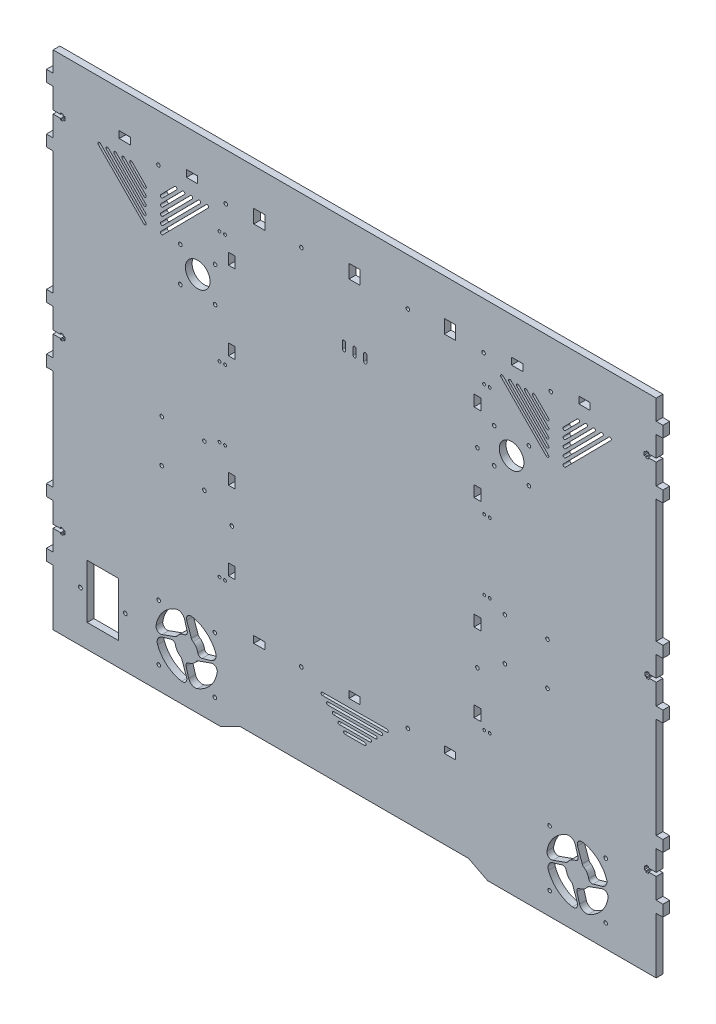
SolidWorks part; units mm, degrees
material "Клен"
ref_plane "Front" through (0, 0, 0) normal (0, 0, 1) x (1, 0, 0)
ref_plane "Top" through (0, 0, 0) normal (0, 1, 0) x (1, 0, 0)
ref_plane "Right" through (0, 0, 0) normal (1, 0, 0) x (0, 0, -1)
sketch "Эскиз1" plane through (0, 0, 0) normal (0, 0, 1) x (1, 0, 0)
  line L3 (1048.7554, 42.0072) -> (1198.2753, 42.0072)
  line L6 (1048.7554, 490.0072) -> (1586.0184, 490.0072)
  line L12 (1586.7554, 42.6812) -> (1586.7554, 42.0072)
  line L13 (1397.7554, 445.0072) -> (1407.7554, 445.0072)
  line L14 (1407.7554, 445.0072) -> (1407.7554, 457.1072)
  line L15 (1407.7554, 457.1072) -> (1397.7554, 457.1072)
  line L16 (1397.7554, 457.1072) -> (1397.7554, 445.0072)
  line L17 (1048.7554, 42.6769) -> (1048.7554, 42.0072)
  line L19 (1503.9666, 426.2291) -> (1516.2724, 438.6716)
  line L20 (1546.3337, 437.0699) -> (1505.9003, 396.1873)
  line L21 (1227.7554, 445.0072) -> (1237.7554, 445.0072)
  line L22 (1237.7554, 445.0072) -> (1237.7554, 457.1072)
  line L23 (1237.7554, 457.1072) -> (1227.7554, 457.1072)
  line L24 (1227.7554, 457.1072) -> (1227.7554, 445.0072)
  line L25 (1312.7554, 445.0072) -> (1322.7554, 445.0072)
  line L26 (1322.7554, 445.0072) -> (1322.7554, 457.1072)
  line L27 (1322.7554, 457.1072) -> (1312.7554, 457.1072)
  line L28 (1312.7554, 457.1072) -> (1312.7554, 445.0072)
  line L38 (1525.1209, 436.9527) -> (1505.7831, 417.4001)
  line L41 (1504.0838, 405.0162) -> (1537.4853, 438.7888)
  line L43 (1504.1228, 397.9452) -> (1544.5562, 438.8279)
  line L44 (1504.0056, 419.1581) -> (1523.3433, 438.7107)
  line L48 (1167.7554, 451.0072) -> (1177.7554, 451.0072)
  line L49 (1177.7554, 451.0072) -> (1177.7554, 457.1072)
  line L50 (1177.7554, 457.1072) -> (1167.7554, 457.1072)
  line L51 (1167.7554, 457.1072) -> (1167.7554, 451.0072)
  line L52 (1518.0499, 436.9136) -> (1505.7441, 424.4711)
  line L53 (1532.1918, 436.9918) -> (1505.8222, 410.3292)
  line L54 (1539.2628, 437.0308) -> (1505.8613, 403.2582)
  line L55 (1504.0447, 412.0872) -> (1530.4143, 438.7498)
  line L56 (1457.7554, 451.0072) -> (1467.7554, 451.0072)
  line L57 (1467.7554, 451.0072) -> (1467.7554, 457.1072)
  line L58 (1467.7554, 457.1072) -> (1457.7554, 457.1072)
  line L59 (1457.7554, 457.1072) -> (1457.7554, 451.0072)
  line L78 (1131.3881, 397.9452) -> (1090.9547, 438.8279)
  line L80 (1089.1772, 437.0699) -> (1129.6105, 396.1873)
  line L82 (1096.2481, 437.0308) -> (1129.6496, 403.2582)
  line L83 (1131.4271, 405.0162) -> (1098.0256, 438.7888)
  line L84 (1131.4662, 412.0872) -> (1105.0966, 438.7498)
  line L85 (1103.3191, 436.9918) -> (1129.6887, 410.3292)
  line L86 (1131.5052, 419.1581) -> (1112.1675, 438.7107)
  line L87 (1110.39, 436.9527) -> (1129.7277, 417.4001)
  line L88 (1131.5443, 426.2291) -> (1119.2385, 438.6716)
  line L89 (1117.461, 436.9136) -> (1129.7668, 424.4711)
  line L90 (1144.921, 397.9452) -> (1185.3543, 438.8279)
  line L91 (1187.1318, 437.0699) -> (1146.6985, 396.1873)
  line L92 (1397.7554, 121.0049) -> (1407.7554, 121.0049)
  line L93 (1407.7554, 121.0049) -> (1407.7554, 127.1049)
  line L94 (1407.7554, 127.1049) -> (1397.7554, 127.1049)
  line L95 (1397.7554, 127.1049) -> (1397.7554, 121.0049)
  line L96 (1312.7554, 121.0049) -> (1322.7554, 121.0049)
  line L97 (1322.7554, 121.0049) -> (1322.7554, 127.1049)
  line L98 (1322.7554, 127.1049) -> (1312.7554, 127.1049)
  line L99 (1312.7554, 127.1049) -> (1312.7554, 121.0049)
  line L100 (1227.7554, 121.0049) -> (1237.7554, 121.0049)
  line L101 (1237.7554, 121.0049) -> (1237.7554, 127.1049)
  line L102 (1237.7554, 127.1049) -> (1227.7554, 127.1049)
  line L143 (1227.7554, 127.1049) -> (1227.7554, 121.0049)
  line L148 (1079.1628, 110.8776) -> (1079.1628, 62.8776)
  line L154 (1455.45, 437.0308) -> (1488.8515, 403.2582)
  line L159 (1107.1628, 110.8776) -> (1079.1628, 110.8776)
  line L160 (1079.1628, 62.8776) -> (1107.1628, 62.8776)
  line L161 (1107.1628, 62.8776) -> (1107.1628, 110.8776)
  line L162 (1144.8819, 405.0162) -> (1178.2834, 438.7888)
  line L163 (1180.0609, 437.0308) -> (1146.6594, 403.2582)
  line L164 (1172.9899, 436.9918) -> (1146.6203, 410.3292)
  line L165 (1144.8428, 412.0872) -> (1171.2124, 438.7498)
  line L166 (1144.8038, 419.1581) -> (1164.1415, 438.7107)
  line L167 (1165.919, 436.9527) -> (1146.5813, 417.4001)
  line L168 (1158.848, 436.9136) -> (1146.5422, 424.4711)
  line L169 (1144.7647, 426.2291) -> (1157.0705, 438.6716)
  line L172 (1326.6292, 91.6177) -> (1309.1294, 91.521)
  line L173 (1309.1156, 94.021) -> (1326.6154, 94.1176)
  line L174 (1331.6015, 96.6452) -> (1304.1019, 96.4933)
  line L175 (1304.0881, 98.9933) -> (1331.5877, 99.1452)
  line L176 (1336.5738, 101.6728) -> (1299.0744, 101.4656)
  line L177 (1299.0605, 103.9656) -> (1336.56, 104.1727)
  line L178 (1289.0054, 113.9102) -> (1346.5046, 114.2278)
  line L179 (1346.5184, 111.7279) -> (1289.0193, 111.4102)
  line L180 (1341.5461, 106.7003) -> (1294.0468, 106.4379)
  line L181 (1294.033, 108.9379) -> (1341.5323, 109.2003)
  line L182 (1490.629, 405.0162) -> (1457.2275, 438.7888)
  line L183 (1448.379, 437.0699) -> (1488.8124, 396.1873)
  line L184 (1469.5919, 436.9527) -> (1488.9296, 417.4001)
  line L185 (1476.6629, 436.9136) -> (1488.9687, 424.4711)
  line L186 (1490.5899, 397.9452) -> (1450.1565, 438.8279)
  line L187 (1490.7071, 419.1581) -> (1471.3694, 438.7107)
  line L188 (1462.521, 436.9918) -> (1488.8906, 410.3292)
  line L189 (1490.7462, 426.2291) -> (1478.4404, 438.6716)
  line L198 (1530.3174, 86.3769) -> (1538.4752, 88.7337)
  line L199 (1494.5571, 86.9094) -> (1506.2002, 91.0661)
  line L200 (1517.0418, 100.6255) -> (1514.685, 108.7833)
  line L201 (1502.7664, 87.3542) -> (1494.6086, 84.9974)
  line L202 (1538.538, 86.8062) -> (1526.8948, 82.6495)
  line L203 (1516.0532, 73.09) -> (1518.4101, 64.9322)
  line L204 (1516.4826, 64.8695) -> (1512.3258, 76.5127)
  line L205 (1516.6012, 108.8616) -> (1520.758, 97.2184)
  line L210 (1215.2753, 50.7072) -> (1198.2753, 42.0072)
  line L268 (1215.2753, 50.7072) -> (1419.2753, 50.7072)
  line L269 (1419.2753, 50.7072) -> (1436.2753, 42.0072)
  line L270 (1436.2753, 42.0072) -> (1586.7554, 42.0072)
  line L271 (1490.6681, 412.0872) -> (1464.2985, 438.7498)
  line L302 (1527.7554, 457.1072) -> (1517.7554, 457.1072)
  line L303 (1517.7554, 451.0072) -> (1527.7554, 451.0072)
  line L304 (1517.7554, 457.1072) -> (1517.7554, 451.0072)
  line L305 (1527.7554, 451.0072) -> (1527.7554, 457.1072)
  line L306 (1117.7554, 451.0072) -> (1117.7554, 457.1072)
  line L307 (1107.7554, 457.1072) -> (1107.7554, 451.0072)
  line L308 (1117.7554, 457.1072) -> (1107.7554, 457.1072)
  line L309 (1107.7554, 451.0072) -> (1117.7554, 451.0072)
  line L310 (1167.825, 64.8695) -> (1163.6683, 76.5127)
  line L348 (1592.7554, 462.0158) -> (1586.7554, 461.9158)
  line L358 (1059.2554, 440.4572) -> (1059.2554, 443.5572)
  line L359 (1057.7554, 439.2572) -> (1057.7554, 440.4572)
  line L360 (1048.7554, 477.0072) -> (1048.7554, 490.0072)
  line L361 (1057.7554, 270.4572) -> (1059.2554, 270.4572)
  line L362 (1055.5554, 270.4572) -> (1055.5554, 269.2572)
  line L363 (1430.3554, 401.9072) -> (1430.3554, 411.9072)
  line L364 (1430.3554, 411.9072) -> (1424.2554, 411.9072)
  line L365 (1424.2554, 411.9072) -> (1424.2554, 401.9072)
  line L366 (1424.2554, 401.9072) -> (1430.3554, 401.9072)
  line L367 (1430.3554, 331.9072) -> (1430.3554, 341.9072)
  line L368 (1430.3554, 341.9072) -> (1424.2554, 341.9072)
  line L369 (1424.2554, 341.9072) -> (1424.2554, 331.9072)
  line L370 (1424.2554, 331.9072) -> (1430.3554, 331.9072)
  line L371 (1430.3554, 231.9072) -> (1430.3554, 241.9072)
  line L372 (1430.3554, 241.9072) -> (1424.2554, 241.9072)
  line L373 (1424.2554, 241.9072) -> (1424.2554, 231.9072)
  line L374 (1424.2554, 231.9072) -> (1430.3554, 231.9072)
  line L375 (1424.2554, 171.9072) -> (1424.2554, 161.9072)
  line L376 (1424.2554, 161.9072) -> (1430.3554, 161.9072)
  line L377 (1430.3554, 161.9072) -> (1430.3554, 171.9072)
  line L378 (1430.3554, 171.9072) -> (1424.2554, 171.9072)
  line L379 (1205.1554, 161.9072) -> (1211.2554, 161.9072)
  line L380 (1211.2554, 161.9072) -> (1211.2554, 171.9072)
  line L381 (1205.1554, 171.9072) -> (1205.1554, 161.9072)
  line L382 (1211.2554, 171.9072) -> (1205.1554, 171.9072)
  line L383 (1211.2554, 231.9072) -> (1211.2554, 241.9072)
  line L384 (1211.2554, 241.9072) -> (1205.1554, 241.9072)
  line L385 (1205.1554, 241.9072) -> (1205.1554, 231.9072)
  line L386 (1205.1554, 231.9072) -> (1211.2554, 231.9072)
  line L387 (1205.1554, 331.9072) -> (1211.2554, 331.9072)
  line L388 (1211.2554, 331.9072) -> (1211.2554, 341.9072)
  line L389 (1205.1554, 341.9072) -> (1205.1554, 331.9072)
  line L390 (1211.2554, 341.9072) -> (1205.1554, 341.9072)
  line L391 (1205.1554, 401.9072) -> (1211.2554, 401.9072)
  line L392 (1211.2554, 401.9072) -> (1211.2554, 411.9072)
  line L393 (1211.2554, 411.9072) -> (1205.1554, 411.9072)
  line L394 (1205.1554, 411.9072) -> (1205.1554, 401.9072)
  line L395 (1145.8995, 86.9094) -> (1157.5427, 91.0661)
  line L396 (1189.8804, 86.8062) -> (1178.2373, 82.6495)
  line L397 (1167.3957, 73.09) -> (1169.7525, 64.9322)
  line L398 (1154.1089, 87.3542) -> (1145.951, 84.9974)
  line L399 (1181.6599, 86.3769) -> (1189.8177, 88.7337)
  line L400 (1167.9437, 108.8616) -> (1172.1004, 97.2184)
  line L414 (1057.7554, 119.2572) -> (1057.7554, 120.4572)
  line L415 (1168.3843, 100.6255) -> (1166.0274, 108.7833)
  line L416 (1317.7554, 12.4246) -> (1317.7554, 537.1765) construction
  line L417 (1586.7554, 537.1765) -> (1586.7554, 12.4246) construction
  line L418 (1048.7554, 537.1765) -> (1048.7554, -11.6164) construction
  line L419 (1042.7554, 92.0072) -> (1042.7554, 102.0072)
  line L422 (1048.7554, 123.5572) -> (1048.7554, 141.9072)
  line L423 (1048.7554, 472.1072) -> (1048.7554, 477.0072)
  line L426 (1059.2554, 123.5572) -> (1057.7554, 123.5572)
  line L427 (1057.7554, 274.7572) -> (1055.5554, 274.7572)
  line L428 (1325.8554, 394.0442) -> (1325.8554, 388.0442)
  line L429 (1328.6554, 388.0442) -> (1328.6554, 394.0442)
  line L430 (1042.7554, 102.0072) -> (1048.7554, 102.1072)
  line L431 (1057.7554, 120.4572) -> (1059.2554, 120.4572)
  line L432 (1316.3554, 394.0442) -> (1316.3554, 388.0442)
  line L433 (1319.1554, 388.0442) -> (1319.1554, 394.0442)
  line L434 (1042.7554, 142.0072) -> (1042.7554, 152.0072)
  line L435 (1042.7554, 302.0072) -> (1048.7554, 302.1072)
  line L436 (1306.8554, 394.0442) -> (1306.8554, 388.0442)
  line L437 (1309.6554, 388.0442) -> (1309.6554, 394.0442)
  line L438 (1055.5554, 120.4572) -> (1055.5554, 119.2572)
  line L439 (1048.7554, 411.9072) -> (1042.7554, 412.0072)
  line L440 (1055.5554, 444.7572) -> (1055.5554, 443.5572)
  line L441 (1057.7554, 124.7572) -> (1055.5554, 124.7572)
  line L442 (1055.5554, 443.5572) -> (1048.7554, 443.5572)
  line L443 (1048.7554, 120.4572) -> (1055.5554, 120.4572)
  line L444 (1042.7554, 242.0072) -> (1042.7554, 252.0072)
  line L445 (1055.5554, 269.2572) -> (1057.7554, 269.2572)
  line L446 (1055.5554, 274.7572) -> (1055.5554, 273.5572)
  line L447 (1048.7554, 461.9072) -> (1042.7554, 462.0072)
  line L448 (1048.7554, 102.1072) -> (1048.7554, 120.4572)
  line L449 (1057.7554, 440.4572) -> (1059.2554, 440.4572)
  line L450 (1048.7554, 252.1072) -> (1048.7554, 270.4572)
  line L451 (1042.7554, 292.0072) -> (1042.7554, 302.0072)
  line L452 (1042.7554, 472.0072) -> (1048.7554, 472.1072)
  line L453 (1059.2554, 443.5572) -> (1057.7554, 443.5572)
  line L454 (1048.7554, 42.6769) -> (1048.7554, 91.9072)
  line L455 (1048.7554, 273.5572) -> (1048.7554, 291.9072)
  line L456 (1055.5554, 440.4572) -> (1055.5554, 439.2572)
  line L457 (1055.5554, 439.2572) -> (1057.7554, 439.2572)
  line L458 (1042.7554, 422.0072) -> (1048.7554, 422.1072)
  line L459 (1048.7554, 443.5572) -> (1048.7554, 461.9072)
  line L460 (1048.7554, 141.9072) -> (1042.7554, 142.0072)
  line L461 (1048.7554, 302.1072) -> (1048.7554, 411.9072)
  line L462 (1048.7554, 91.9072) -> (1042.7554, 92.0072)
  line L463 (1048.7554, 270.4572) -> (1055.5554, 270.4572)
  line L464 (1048.7554, 291.9072) -> (1042.7554, 292.0072)
  line L465 (1059.2554, 120.4572) -> (1059.2554, 123.5572)
  line L466 (1057.7554, 273.5572) -> (1057.7554, 274.7572)
  line L467 (1042.7554, 252.0072) -> (1048.7554, 252.1072)
  line L468 (1059.2554, 273.5572) -> (1057.7554, 273.5572)
  line L469 (1048.7554, 422.1072) -> (1048.7554, 440.4572)
  line L470 (1042.7554, 462.0072) -> (1042.7554, 472.0072)
  line L471 (1057.7554, 269.2572) -> (1057.7554, 270.4572)
  line L472 (1057.7554, 443.5572) -> (1057.7554, 444.7572)
  line L473 (1042.7554, 152.0072) -> (1048.7554, 152.1072)
  line L474 (1059.2554, 270.4572) -> (1059.2554, 273.5572)
  line L475 (1055.5554, 273.5572) -> (1048.7554, 273.5572)
  line L476 (1048.7554, 152.1072) -> (1048.7554, 241.9072)
  line L477 (1057.7554, 444.7572) -> (1055.5554, 444.7572)
  line L478 (1055.5554, 124.7572) -> (1055.5554, 123.5572)
  line L479 (1048.7554, 241.9072) -> (1042.7554, 242.0072)
  line L480 (1055.5554, 123.5572) -> (1048.7554, 123.5572)
  line L481 (1057.7554, 123.5572) -> (1057.7554, 124.7572)
  line L482 (1055.5554, 119.2572) -> (1057.7554, 119.2572)
  line L483 (1042.7554, 412.0072) -> (1042.7554, 422.0072)
  line L484 (1048.7554, 440.4572) -> (1055.5554, 440.4572)
  line L487 (1586.0184, 490.0072) -> (1586.7554, 490.0072)
  line L488 (1586.7554, 302.1072) -> (1592.7554, 302.0072)
  line L489 (1592.7554, 252.0072) -> (1592.7554, 242.0072)
  line L490 (1579.6985, 444.7615) -> (1577.4985, 444.7615)
  line L491 (1592.7554, 472.0072) -> (1592.7554, 462.0158)
  line L492 (1579.9554, 120.4572) -> (1586.7554, 120.4572)
  line L493 (1592.7554, 102.0072) -> (1592.7554, 92.0072)
  line L494 (1579.9554, 123.5572) -> (1579.9554, 124.7572)
  line L495 (1586.7554, 490.0072) -> (1586.7554, 472.1072)
  line L496 (1577.7554, 120.4572) -> (1577.7554, 119.2572)
  line L497 (1578.2356, 269.2572) -> (1580.4356, 269.2572)
  line L498 (1575.9985, 440.4615) -> (1577.4985, 440.4615)
  line L499 (1580.4356, 274.7572) -> (1578.2356, 274.7572)
  line L500 (1577.7554, 123.5572) -> (1576.2554, 123.5572)
  line L501 (1576.7356, 273.5572) -> (1576.7356, 270.4572)
  line L502 (1586.4985, 443.5615) -> (1586.7554, 443.5615)
  line L503 (1578.2356, 274.7572) -> (1578.2356, 273.5572)
  line L504 (1577.4985, 439.2615) -> (1579.6985, 439.2615)
  line L505 (1576.2554, 120.4572) -> (1577.7554, 120.4572)
  line L506 (1586.4985, 443.5615) -> (1579.6985, 443.5615)
  line L507 (1586.7554, 141.9072) -> (1586.7554, 123.5572)
  line L508 (1592.7554, 142.0072) -> (1586.7554, 141.9072)
  line L509 (1586.7554, 252.1072) -> (1592.7554, 252.0072)
  line L510 (1578.2356, 270.4572) -> (1578.2356, 269.2572)
  line L511 (1580.4356, 270.4572) -> (1586.7554, 270.4572)
  line L512 (1579.9554, 124.7572) -> (1577.7554, 124.7572)
  line L513 (1577.7554, 124.7572) -> (1577.7554, 123.5572)
  line L514 (1592.7554, 142.0072) -> (1592.7554, 152.0072)
  line L515 (1579.6985, 440.4615) -> (1586.4985, 440.4615)
  line L516 (1592.7554, 412.0072) -> (1586.7554, 411.9072)
  line L517 (1580.4356, 269.2572) -> (1580.4356, 270.4572)
  line L518 (1586.7554, 91.9072) -> (1586.7554, 42.6812)
  line L519 (1592.7554, 242.0072) -> (1586.7554, 241.9072)
  line L520 (1579.6985, 439.2615) -> (1579.6985, 440.4615)
  line L521 (1580.4356, 273.5572) -> (1580.4356, 274.7572)
  line L522 (1586.7554, 270.4572) -> (1586.7554, 252.1072)
  line L523 (1577.4985, 443.5615) -> (1575.9985, 443.5615)
  line L524 (1586.7554, 152.1072) -> (1592.7554, 152.0072)
  line L525 (1577.7554, 119.2572) -> (1579.9554, 119.2572)
  line L526 (1592.7554, 422.0072) -> (1592.7554, 412.0072)
  line L527 (1586.7554, 422.1072) -> (1592.7554, 422.0072)
  line L528 (1579.9554, 119.2572) -> (1579.9554, 120.4572)
  line L529 (1586.7554, 273.5572) -> (1580.4356, 273.5572)
  line L530 (1586.7554, 123.5572) -> (1579.9554, 123.5572)
  line L531 (1586.4985, 440.4615) -> (1586.7554, 440.4615)
  line L532 (1576.7356, 270.4572) -> (1578.2356, 270.4572)
  line L533 (1586.7554, 461.9158) -> (1586.7554, 443.5615)
  line L534 (1575.9985, 443.5615) -> (1575.9985, 440.4615)
  line L535 (1592.7554, 292.0072) -> (1586.7554, 291.9072)
  line L536 (1586.7554, 120.4572) -> (1586.7554, 102.1072)
  line L537 (1576.2554, 123.5572) -> (1576.2554, 120.4572)
  line L538 (1586.7554, 102.1072) -> (1592.7554, 102.0072)
  line L539 (1592.7554, 92.0072) -> (1586.7554, 91.9072)
  line L540 (1586.7554, 411.9072) -> (1586.7554, 302.1072)
  line L541 (1592.7554, 302.0072) -> (1592.7554, 292.0072)
  line L542 (1577.4985, 444.7615) -> (1577.4985, 443.5615)
  line L543 (1579.6985, 443.5615) -> (1579.6985, 444.7615)
  line L544 (1586.7554, 241.9072) -> (1586.7554, 152.1072)
  line L545 (1586.7554, 440.4615) -> (1586.7554, 422.1072)
  line L546 (1586.7554, 291.9072) -> (1586.7554, 273.5572)
  line L547 (1578.2356, 273.5572) -> (1576.7356, 273.5572)
  line L548 (1586.7554, 472.1072) -> (1592.7554, 472.0072)
  line L549 (1577.4985, 440.4615) -> (1577.4985, 439.2615)
  circle A0 centre (1193.2554, 365.5072) radius 1.6
  circle A1 centre (1162.2554, 365.5072) radius 1.6
  circle A2 centre (1177.7554, 381.0072) radius 11
  circle A3 centre (1193.2554, 396.5072) radius 1.6
  circle A4 centre (1202.7554, 448.0572) radius 1.6
  circle A5 centre (1432.7554, 448.0572) radius 1.6
  circle A6 centre (1365.2554, 448.0572) radius 1.6
  circle A7 centre (1270.2554, 448.0572) radius 1.6
  circle A12 centre (1162.2554, 396.5072) radius 1.6
  circle A13 centre (1145.7129, 217.2739) radius 1.6
  circle A14 centre (1365.2554, 124.0549) radius 1.6
  circle A15 centre (1270.2554, 124.0549) radius 1.6
  circle A20 centre (1492.7554, 448.0572) radius 1.6
  circle A21 centre (1142.7554, 448.0572) radius 1.6
  circle A24 centre (1073.1628, 86.8776) radius 1.65
  circle A25 centre (1113.1628, 86.8776) radius 1.65
  circle A26 centre (1145.7129, 255.2739) radius 1.6
  circle A27 centre (1183.7129, 217.2739) radius 1.6
  circle A28 centre (1183.7129, 255.2739) radius 1.6
  arc A29 (1504.0056, 419.1581) -> (1505.7831, 417.4001) centre (1504.8944, 418.2791) ccw
  arc A30 (1503.9666, 426.2291) -> (1505.7441, 424.4711) centre (1504.8553, 425.3501) ccw
  arc A31 (1504.1228, 397.9452) -> (1505.9003, 396.1873) centre (1505.0116, 397.0662) ccw
  arc A32 (1518.0499, 436.9136) -> (1516.2724, 438.6716) centre (1517.1611, 437.7926) ccw
  arc A33 (1504.0447, 412.0872) -> (1505.8222, 410.3292) centre (1504.9335, 411.2082) ccw
  arc A34 (1546.3337, 437.0699) -> (1544.5562, 438.8279) centre (1545.445, 437.9489) ccw
  arc A35 (1539.2628, 437.0308) -> (1537.4853, 438.7888) centre (1538.374, 437.9098) ccw
  arc A36 (1326.6292, 91.6177) -> (1326.6154, 94.1176) centre (1326.6223, 92.8677) ccw
  arc A37 (1309.1156, 94.021) -> (1309.1294, 91.521) centre (1309.1225, 92.771) ccw
  arc A38 (1304.0881, 98.9933) -> (1304.1019, 96.4933) centre (1304.095, 97.7433) ccw
  arc A39 (1331.6015, 96.6452) -> (1331.5877, 99.1452) centre (1331.5946, 97.8952) ccw
  arc A40 (1336.5738, 101.6728) -> (1336.56, 104.1727) centre (1336.5669, 102.9228) ccw
  arc A41 (1299.0605, 103.9656) -> (1299.0744, 101.4656) centre (1299.0674, 102.7156) ccw
  arc A42 (1294.033, 108.9379) -> (1294.0468, 106.4379) centre (1294.0399, 107.6879) ccw
  arc A43 (1341.5461, 106.7003) -> (1341.5323, 109.2003) centre (1341.5392, 107.9503) ccw
  arc A44 (1346.5184, 111.7279) -> (1346.5046, 114.2278) centre (1346.5115, 112.9779) ccw
  arc A45 (1289.0054, 113.9102) -> (1289.0193, 111.4102) centre (1289.0124, 112.6602) ccw
  arc A46 (1157.5427, 91.0661) -> (1159.5017, 92.5785) centre (1156.1978, 94.8332) ccw
  arc A47 (1450.1565, 438.8279) -> (1448.379, 437.0699) centre (1449.2678, 437.9489) ccw
  arc A48 (1471.3694, 438.7107) -> (1469.5919, 436.9527) centre (1470.4807, 437.8317) ccw
  arc A49 (1457.2275, 438.7888) -> (1455.45, 437.0308) centre (1456.3388, 437.9098) ccw
  arc A50 (1488.9687, 424.4711) -> (1490.7462, 426.2291) centre (1489.8574, 425.3501) ccw
  arc A51 (1488.8515, 403.2582) -> (1490.629, 405.0162) centre (1489.7403, 404.1372) ccw
  arc A52 (1488.8124, 396.1873) -> (1490.5899, 397.9452) centre (1489.7012, 397.0662) ccw
  arc A53 (1488.8906, 410.3292) -> (1490.6681, 412.0872) centre (1489.7793, 411.2082) ccw
  arc A54 (1488.9296, 417.4001) -> (1490.7071, 419.1581) centre (1489.8184, 418.2791) ccw
  arc A55 (1478.4404, 438.6716) -> (1476.6629, 436.9136) centre (1477.5516, 437.7926) ccw
  arc A56 (1464.2985, 438.7498) -> (1462.521, 436.9918) centre (1463.4097, 437.8708) ccw
  arc A67 (1166.0274, 108.7833) -> (1158.15, 112.7336) centre (1160.2632, 107.118) ccw
  arc A68 (1189.8177, 88.7337) -> (1193.7679, 96.6112) centre (1188.1523, 94.498) ccw
  circle A69 centre (1143.0318, 112.013) radius 1.6
  circle A70 centre (1143.0318, 62.013) radius 1.6
  arc A71 (1166.0477, 96.8429) -> (1168.3843, 100.6255) centre (1165.5021, 99.7929) ccw
  arc A72 (1145.951, 84.9974) -> (1142.0008, 77.1199) centre (1147.6164, 79.2331) ccw
  arc A100 (1178.2373, 82.6495) -> (1176.2782, 81.1371) centre (1179.5822, 78.8823) ccw
  arc A102 (1538.4752, 88.7337) -> (1542.4254, 96.6112) centre (1536.8099, 94.498) ccw
  arc A103 (1526.2875, 60.982) -> (1543.8306, 82.3942) centre (1516.5531, 86.85) ccw
  arc A104 (1512.3258, 76.5127) -> (1510.8135, 78.4717) centre (1508.5587, 75.1677) ccw
  arc A105 (1518.3898, 76.8727) -> (1516.0532, 73.09) centre (1518.9354, 73.9227) ccw
  arc A106 (1489.2645, 91.3213) -> (1494.5571, 86.9094) centre (1493.2122, 90.6765) ccw
  arc A107 (1512.0706, 59.5769) -> (1516.4826, 64.8695) centre (1512.7155, 63.5246) ccw
  arc A108 (1506.2002, 91.0661) -> (1508.1593, 92.5785) centre (1504.8553, 94.8332) ccw
  arc A109 (1521.0132, 114.1542) -> (1516.6012, 108.8616) centre (1520.3684, 110.2065) ccw
  arc A110 (1518.3898, 76.8727) -> (1524.9358, 81.1371) centre (1516.5419, 86.8655) ccw
  circle A111 centre (1541.6893, 112.013) radius 1.6
  arc A112 (1494.6086, 84.9974) -> (1490.6584, 77.1199) centre (1496.2739, 79.2331) ccw
  arc A113 (1506.5491, 85.0176) -> (1510.8135, 78.4717) centre (1516.5419, 86.8655) ccw
  arc A114 (1526.8948, 82.6495) -> (1524.9358, 81.1371) centre (1528.2397, 78.8823) ccw
  circle A115 centre (1541.6893, 62.013) radius 1.6
  arc A116 (1490.6584, 77.1199) -> (1512.0706, 59.5769) centre (1516.5264, 86.8543) ccw
  arc A117 (1514.685, 108.7833) -> (1506.8075, 112.7336) centre (1508.9207, 107.118) ccw
  circle A118 centre (1491.6893, 112.013) radius 1.6
  arc A119 (1520.758, 97.2184) -> (1522.2703, 95.2594) centre (1524.5251, 98.5634) ccw
  arc A120 (1542.4254, 96.6112) -> (1521.0132, 114.1542) centre (1516.5574, 86.8768) ccw
  arc A121 (1526.5348, 88.7135) -> (1522.2703, 95.2594) centre (1516.5419, 86.8655) ccw
  arc A122 (1506.8075, 112.7336) -> (1489.2645, 91.3213) centre (1516.5419, 86.8655) ccw
  arc A123 (1506.5491, 85.0176) -> (1502.7664, 87.3542) centre (1503.5991, 84.4721) ccw
  arc A124 (1514.7052, 96.8429) -> (1508.1593, 92.5785) centre (1516.5531, 86.85) ccw
  arc A125 (1543.8306, 82.3942) -> (1538.538, 86.8062) centre (1539.8829, 83.0391) ccw
  circle A126 centre (1491.6893, 62.013) radius 1.6
  arc A127 (1518.4101, 64.9322) -> (1526.2875, 60.982) centre (1524.1743, 66.5976) ccw
  arc A128 (1526.5348, 88.7135) -> (1530.3174, 86.3769) centre (1529.4848, 89.259) ccw
  arc A129 (1514.7052, 96.8429) -> (1517.0418, 100.6255) centre (1514.1597, 99.7929) ccw
  arc A130 (1157.8915, 85.0176) -> (1154.1089, 87.3542) centre (1154.9415, 84.4721) ccw
  arc A131 (1172.3557, 114.1542) -> (1167.9437, 108.8616) centre (1171.7108, 110.2065) ccw
  arc A132 (1172.1004, 97.2184) -> (1173.6128, 95.2594) centre (1175.8676, 98.5634) ccw
  arc A133 (1177.63, 60.982) -> (1195.173, 82.3942) centre (1167.8956, 86.85) ccw
  arc A134 (1193.7679, 96.6112) -> (1172.3557, 114.1542) centre (1167.8999, 86.8768) ccw
  circle A135 centre (1193.0318, 62.013) radius 1.6
  arc A136 (1166.0477, 96.8429) -> (1159.5017, 92.5785) centre (1167.8956, 86.85) ccw
  arc A137 (1169.7525, 64.9322) -> (1177.63, 60.982) centre (1175.5168, 66.5976) ccw
  arc A138 (1169.7323, 76.8727) -> (1176.2782, 81.1371) centre (1167.8844, 86.8655) ccw
  arc A139 (1177.8772, 88.7135) -> (1173.6128, 95.2594) centre (1167.8844, 86.8655) ccw
  arc A160 (1169.7323, 76.8727) -> (1167.3957, 73.09) centre (1170.2778, 73.9227) ccw
  arc A161 (1157.8915, 85.0176) -> (1162.1559, 78.4717) centre (1167.8844, 86.8655) ccw
  arc A162 (1163.4131, 59.5769) -> (1167.825, 64.8695) centre (1164.0579, 63.5246) ccw
  arc A163 (1142.0008, 77.1199) -> (1163.4131, 59.5769) centre (1167.8688, 86.8543) ccw
  arc A164 (1163.6683, 76.5127) -> (1162.1559, 78.4717) centre (1159.9012, 75.1677) ccw
  arc A165 (1195.173, 82.3942) -> (1189.8804, 86.8062) centre (1191.2253, 83.0391) ccw
  arc A166 (1177.8772, 88.7135) -> (1181.6599, 86.3769) centre (1180.8272, 89.259) ccw
  circle A167 centre (1193.0318, 112.013) radius 1.6
  arc A168 (1158.15, 112.7336) -> (1140.6069, 91.3213) centre (1167.8844, 86.8655) ccw
  arc A169 (1140.6069, 91.3213) -> (1145.8995, 86.9094) centre (1144.5546, 90.6765) ccw
  arc A190 (1532.1918, 436.9918) -> (1530.4143, 438.7498) centre (1531.3031, 437.8708) ccw
  arc A191 (1525.1209, 436.9527) -> (1523.3433, 438.7107) centre (1524.2321, 437.8317) ccw
  arc A192 (1504.0838, 405.0162) -> (1505.8613, 403.2582) centre (1504.9725, 404.1372) ccw
  arc A193 (1089.1772, 437.0699) -> (1090.9547, 438.8279) centre (1090.0659, 437.9489) cw
  circle A194 centre (1427.3054, 371.9072) radius 1.6
  circle A195 centre (1427.3054, 201.9072) radius 1.6
  circle A196 centre (1208.2054, 201.9072) radius 1.6
  arc A198 (1131.3881, 397.9452) -> (1129.6105, 396.1873) centre (1130.4993, 397.0662) cw
  arc A199 (1131.4271, 405.0162) -> (1129.6496, 403.2582) centre (1130.5384, 404.1372) cw
  arc A200 (1096.2481, 437.0308) -> (1098.0256, 438.7888) centre (1097.1369, 437.9098) cw
  arc A201 (1103.3191, 436.9918) -> (1105.0966, 438.7498) centre (1104.2078, 437.8708) cw
  arc A202 (1131.4662, 412.0872) -> (1129.6887, 410.3292) centre (1130.5774, 411.2082) cw
  arc A203 (1110.39, 436.9527) -> (1112.1675, 438.7107) centre (1111.2788, 437.8317) cw
  arc A216 (1131.5052, 419.1581) -> (1129.7277, 417.4001) centre (1130.6165, 418.2791) cw
  arc A217 (1117.461, 436.9136) -> (1119.2385, 438.6716) centre (1118.3497, 437.7926) cw
  arc A218 (1131.5443, 426.2291) -> (1129.7668, 424.4711) centre (1130.6556, 425.3501) cw
  arc A219 (1146.6985, 396.1873) -> (1144.921, 397.9452) centre (1145.8097, 397.0662) cw
  circle A220 centre (1202.1959, 261.1916) radius 1.25
  circle A221 centre (1197.2245, 261.2595) radius 1.25
  circle A228 centre (1202.1586, 156.838) radius 1.25
  circle A229 centre (1197.1872, 156.9059) radius 1.25
  arc A230 (1185.3543, 438.8279) -> (1187.1318, 437.0699) centre (1186.2431, 437.9489) cw
  arc A231 (1178.2834, 438.7888) -> (1180.0609, 437.0308) centre (1179.1721, 437.9098) cw
  circle A232 centre (1438.3088, 156.7702) radius 1.25
  arc A233 (1146.6594, 403.2582) -> (1144.8819, 405.0162) centre (1145.7706, 404.1372) cw
  circle A234 centre (1433.3374, 156.838) radius 1.25
  arc A235 (1171.2124, 438.7498) -> (1172.9899, 436.9918) centre (1172.1012, 437.8708) cw
  arc A237 (1146.6203, 410.3292) -> (1144.8428, 412.0872) centre (1145.7316, 411.2082) cw
  arc A239 (1146.5813, 417.4001) -> (1144.8038, 419.1581) centre (1145.6925, 418.2791) cw
  arc A241 (1164.1415, 438.7107) -> (1165.919, 436.9527) centre (1165.0302, 437.8317) cw
  arc A243 (1157.0705, 438.6716) -> (1158.848, 436.9136) centre (1157.9593, 437.7926) cw
  arc A245 (1146.5422, 424.4711) -> (1144.7647, 426.2291) centre (1145.6534, 425.3501) cw
  circle A247 centre (1473.2554, 365.5072) radius 1.6
  circle A248 centre (1438.3461, 261.1238) radius 1.25
  circle A249 centre (1442.2554, 365.5072) radius 1.6
  circle A250 centre (1433.3748, 261.1916) radius 1.25
  circle A251 centre (1442.2554, 396.5072) radius 1.6
  circle A252 centre (1438.3268, 323.4135) radius 1.25
  circle A253 centre (1457.7554, 381.0072) radius 11
  circle A254 centre (1433.3554, 323.4814) radius 1.25
  circle A255 centre (1473.2554, 396.5072) radius 1.6
  circle A256 centre (1489.798, 217.2739) radius 1.6
  circle A257 centre (1451.798, 217.2739) radius 1.6
  circle A261 centre (1451.798, 255.2739) radius 1.6
  circle A263 centre (1489.798, 255.2739) radius 1.6
  circle A268 centre (1438.1921, 423.9311) radius 1.25
  circle A270 centre (1433.2207, 423.999) radius 1.25
  circle A280 centre (1202.1766, 323.4814) radius 1.25
  circle A282 centre (1197.2052, 323.5492) radius 1.25
  circle A298 centre (1197.1679, 424.0668) radius 1.25
  circle A300 centre (1202.1392, 423.999) radius 1.25
  arc A312 (1325.8554, 388.0442) -> (1328.6554, 388.0442) centre (1327.2554, 388.0442) ccw
  arc A313 (1328.6554, 394.0442) -> (1325.8554, 394.0442) centre (1327.2554, 394.0442) ccw
  arc A316 (1316.3554, 388.0442) -> (1319.1554, 388.0442) centre (1317.7554, 388.0442) ccw
  arc A317 (1319.1554, 394.0442) -> (1316.3554, 394.0442) centre (1317.7554, 394.0442) ccw
  arc A320 (1306.8554, 388.0442) -> (1309.6554, 388.0442) centre (1308.2554, 388.0442) ccw
  arc A321 (1309.6554, 394.0442) -> (1306.8554, 394.0442) centre (1308.2554, 394.0442) ccw
  dimension "D3" = 269
  dimension "D4" = 15.5
  dimension "D5" = 31
  dimension "D6" = 31
  dimension "D2" = 269
  dimension "D8" = 31
  dimension "D9" = 109
  dimension "D1" = 149.5198
  dimension "D7" = 13
extrude "Бобышка-Вытянуть1" add sketch "Эскиз1" against normal blind 6
